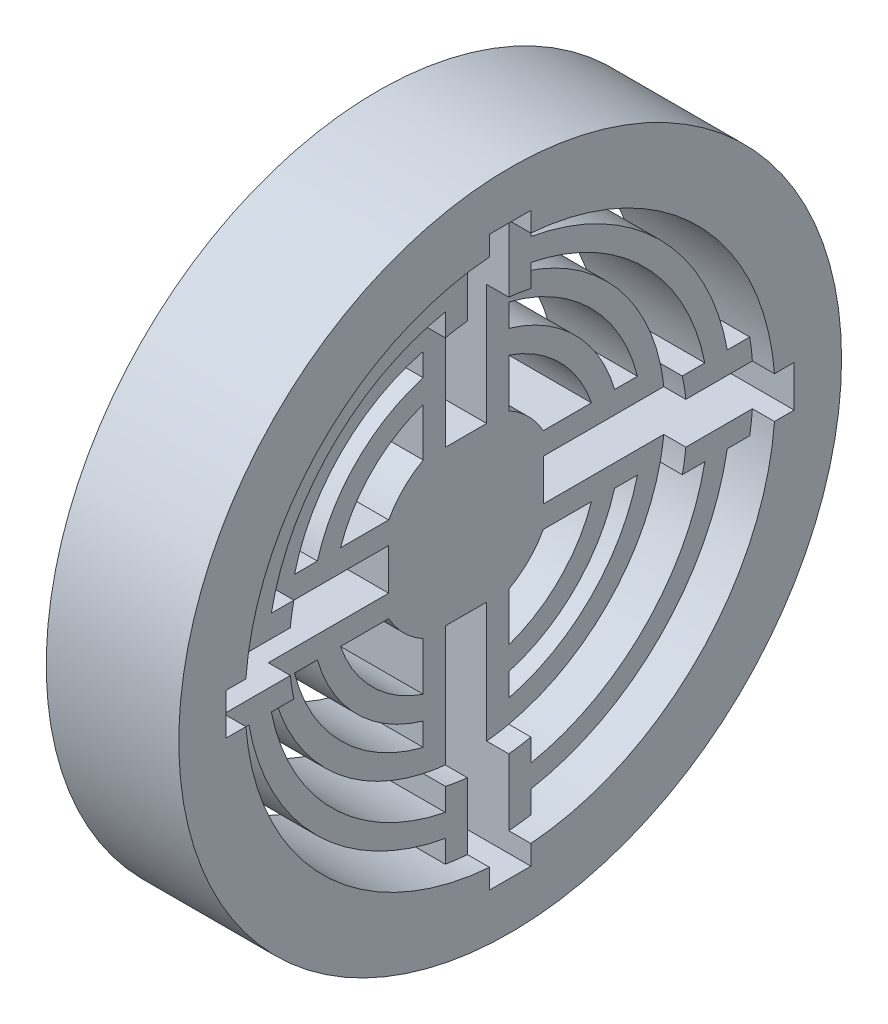
SolidWorks part; units mm, degrees
ref_plane "Front Plane" through (0, 0, 0) normal (0, 0, 1) x (1, 0, 0)
ref_plane "Top Plane" through (0, 0, 0) normal (0, 1, 0) x (1, 0, 0)
ref_plane "Right Plane" through (0, 0, 0) normal (1, 0, 0) x (0, 0, -1)
sketch "Sketch1" plane through (0, 0, 0) normal (1, 0, 0) x (0, 0, -1)
  line L0 (-0.9679, 1.7502) -> (-0.9679, 6.4275)
  line L2 (0.9679, -6.4275) -> (0.9679, -1.7502)
  line L4 (-0.9679, -6.4275) -> (-0.9679, -1.7502)
  line L5 (-1.7502, 0.4679) -> (-6.4276, 0.4679)
  line L6 (6.4276, -0.4679) -> (1.7502, -0.4679)
  line L7 (6.4275, -0.9679) -> (1.7502, -0.9679)
  line L9 (6.4275, 0.9679) -> (1.7502, 0.9679)
  line L11 (6.4276, -0.4679) -> (6.4276, 0.4679)
  line L12 (6.4276, 0.4679) -> (1.7502, 0.4679)
  line L13 (-6.4276, -0.4679) -> (-6.4276, 0.4679)
  line L14 (1.7502, 0.9679) -> (1.7502, -0.9679)
  line L15 (0.9679, 1.7502) -> (0.9679, 6.4275)
  line L16 (-1.7502, 0.9679) -> (-6.4275, 0.9679)
  line L17 (0.9679, -1.7502) -> (-0.9679, -1.7502)
  line L18 (-1.7502, -0.9679) -> (-6.4275, -0.9679)
  line L19 (-0.4679, -6.4276) -> (0.4679, -6.4276)
  line L20 (-0.4679, -6.4276) -> (-0.4679, -1.7502)
  line L21 (-0.4679, 6.4276) -> (0.4679, 6.4276)
  line L22 (0.4679, -6.4276) -> (0.4679, -1.7502)
  line L23 (-1.7502, -0.9679) -> (-1.7502, 0.9679)
  line L24 (-0.9679, 1.7502) -> (0.9679, 1.7502)
  line L25 (-6.4275, 0.9679) -> (-6.4275, -0.9679)
  line L26 (-1.7502, -0.4679) -> (-6.4276, -0.4679)
  line L27 (-0.9679, -6.4275) -> (0.9679, -6.4275)
  line L28 (0.4679, 1.7502) -> (0.4679, 6.4276)
  line L29 (6.4275, 0.9679) -> (6.4275, -0.9679)
  line L30 (-0.9679, 6.4275) -> (0.9679, 6.4275)
  line L31 (-0.4679, 1.7502) -> (-0.4679, 6.4276)
  circle A0 centre (0, 0) radius 7.5
  arc A1 (-0.9679, 6.4275) -> (-6.4275, 0.9679) centre (0, 0) ccw
  arc A2 (-5.9214, -0.9679) -> (-0.9679, -5.9214) centre (0, 0) ccw
  arc A3 (-5.4142, -0.9679) -> (-0.9679, -5.4142) centre (0, 0) ccw
  arc A4 (-4.9054, -0.9679) -> (-0.9679, -4.9054) centre (0, 0) ccw
  arc A5 (-4.3947, -0.9679) -> (-0.9679, -4.3947) centre (0, 0) ccw
  arc A6 (-3.8811, -0.9679) -> (-0.9679, -3.8811) centre (0, 0) ccw
  arc A7 (-2.8396, -0.9679) -> (-0.9679, -2.8396) centre (0, 0) ccw
  arc A8 (-1.7502, -0.9679) -> (-0.9679, -1.7502) centre (0, 0) ccw
  arc A9 (-6.4275, -0.9679) -> (-0.9679, -6.4275) centre (0, 0) ccw
  arc A10 (0.9679, -6.4275) -> (6.4275, -0.9679) centre (0, 0) ccw
  arc A11 (6.4275, 0.9679) -> (0.9679, 6.4275) centre (0, 0) ccw
  arc A12 (2.8396, 0.9679) -> (0.9679, 2.8396) centre (0, 0) ccw
  arc A13 (3.8811, 0.9679) -> (0.9679, 3.8811) centre (0, 0) ccw
  arc A14 (4.3947, 0.9679) -> (0.9679, 4.3947) centre (0, 0) ccw
  arc A15 (4.9054, 0.9679) -> (0.9679, 4.9054) centre (0, 0) ccw
  arc A16 (5.4142, 0.9679) -> (0.9679, 5.4142) centre (0, 0) ccw
  arc A17 (5.9214, 0.9679) -> (0.9679, 5.9214) centre (0, 0) ccw
  arc A18 (-0.9679, 5.9214) -> (-5.9214, 0.9679) centre (0, 0) ccw
  arc A19 (-0.9679, 5.4142) -> (-5.4142, 0.9679) centre (0, 0) ccw
  arc A20 (-0.9679, 4.9054) -> (-4.9054, 0.9679) centre (0, 0) ccw
  arc A21 (-0.9679, 4.3947) -> (-4.3947, 0.9679) centre (0, 0) ccw
  arc A22 (-0.9679, 3.8811) -> (-3.8811, 0.9679) centre (0, 0) ccw
  arc A23 (-0.9679, 2.8396) -> (-2.8396, 0.9679) centre (0, 0) ccw
  arc A24 (0.9679, -2.8396) -> (2.8396, -0.9679) centre (0, 0) ccw
  arc A25 (0.9679, -3.8811) -> (3.8811, -0.9679) centre (0, 0) ccw
  arc A26 (0.9679, -4.3947) -> (4.3947, -0.9679) centre (0, 0) ccw
  arc A27 (0.9679, -4.9054) -> (4.9054, -0.9679) centre (0, 0) ccw
  arc A28 (0.9679, -5.4142) -> (5.4142, -0.9679) centre (0, 0) ccw
  arc A29 (0.9679, -5.9214) -> (5.9214, -0.9679) centre (0, 0) ccw
  arc A30 (-3.3635, -0.9679) -> (-0.9679, -3.3635) centre (0, 0) ccw
  arc A31 (3.3635, 0.9679) -> (0.9679, 3.3635) centre (0, 0) ccw
  arc A32 (-0.9679, 3.3635) -> (-3.3635, 0.9679) centre (0, 0) ccw
  arc A33 (0.9679, -3.3635) -> (3.3635, -0.9679) centre (0, 0) ccw
  arc A34 (1.7502, 0.9679) -> (0.9679, 1.7502) centre (0, 0) ccw
  arc A35 (-0.9679, 1.7502) -> (-1.7502, 0.9679) centre (0, 0) ccw
  arc A36 (0.9679, -1.7502) -> (1.7502, -0.9679) centre (0, 0) ccw
  dimension "D1" = 15
  dimension "D2" = 4
  dimension "D3" = 1
  dimension "D4" = 1
  dimension "D5" = 1
  dimension "D6" = 0.5
  dimension "D7" = 0.5
  dimension "D8" = 0.5
  dimension "D9" = 0.5
  dimension "D15" = 0.5
  dimension "D10" = 12.8551
  dimension "D11" = 12.8551
  dimension "D12" = 0.5
  dimension "D13" = 4.6773
  dimension "D14" = 4.6773
  dimension "D16" = 0.5
  dimension "D17" = 0.5
  dimension "D18" = 0.5
extrude "Boss-Extrude1" add sketch "Sketch1" along normal blind 3 contours A0 A11 L29 L12 L11 L6 A10 L27 L22 L19 L20 A9 L25 L26 L13 L5 A1 L30 L31 L21 L28 | L17 A36 L14 A34 L24 A35 L23 A8 | L9 A31 L15 A12 | L9 A14 L15 A13 | L9 A16 L15 A15 | A17 L9 A11 L15 | A18 L0 A1 L16 | L18 A9 L4 A2 | A29 L2 A10 L7 | L2 A28 L7 A27 | A4 L18 A3 L4 | A6 L18 A5 L4 | L18 A30 L4 A7 | L2 A26 L7 A25 | L2 A33 L7 A24 | L0 A32 L16 A23 | A22 L0 A21 L16 | A20 L0 A19 L16 | L30 L28 L24 L15 | L23 L26 L25 L18 | L22 L27 L2 L17 | L29 L9 L14 L12 | L29 L6 L14 L7 | L4 L27 L20 L17 | L16 L25 L5 L23 | L24 L31 L30 L0 region at (0, 4.0889, 0.7179) region at (0, 0, 0) region at (0, 2.2165, 2.2165) region at (0, 0.7179, 4.0889) region at (0, 4.0889, -0.7179) region at (0, 2.8574, 2.8574) region at (0, 6.1745, 1.0451) region at (0, -0.7179, 4.0889) region at (0, 2.2165, -2.2165) region at (0, 0.7179, -4.0889) region at (0, 4.5416, -4.5416) region at (0, 3.58, 3.58) region at (0, -1.0451, 6.1745) region at (0, -2.2165, 2.2165) region at (0, -4.0889, 0.7179) region at (0, 2.8574, -2.8574) region at (0, -0.7179, -4.0889) region at (0, 3.8446, -3.8446) region at (0, -1.0308, 5.1598) region at (0, -2.8574, 2.8574) region at (0, -4.0889, -0.7179) region at (0, -4.5416, -4.5416) region at (0, -2.2165, -2.2165) region at (0, -3.8446, -3.8446) region at (0, -2.8574, -2.8574) region at (0, 0, 7.2879)
sketch "Sketch2" plane through (3, 0, 0) normal (1, 0, 0) x (0, 0, -1)
  circle A0 centre (0, 0) radius 6
extrude "Cut-Extrude1" cut sketch "Sketch2" against normal blind 0.5
sketch "Sketch3" plane through (2.5, 0, 0) normal (1, 0, 0) x (0, 0, -1)
  circle A0 centre (0, 0) radius 4.5
extrude "Cut-Extrude2" cut sketch "Sketch3" against normal blind 0.5
